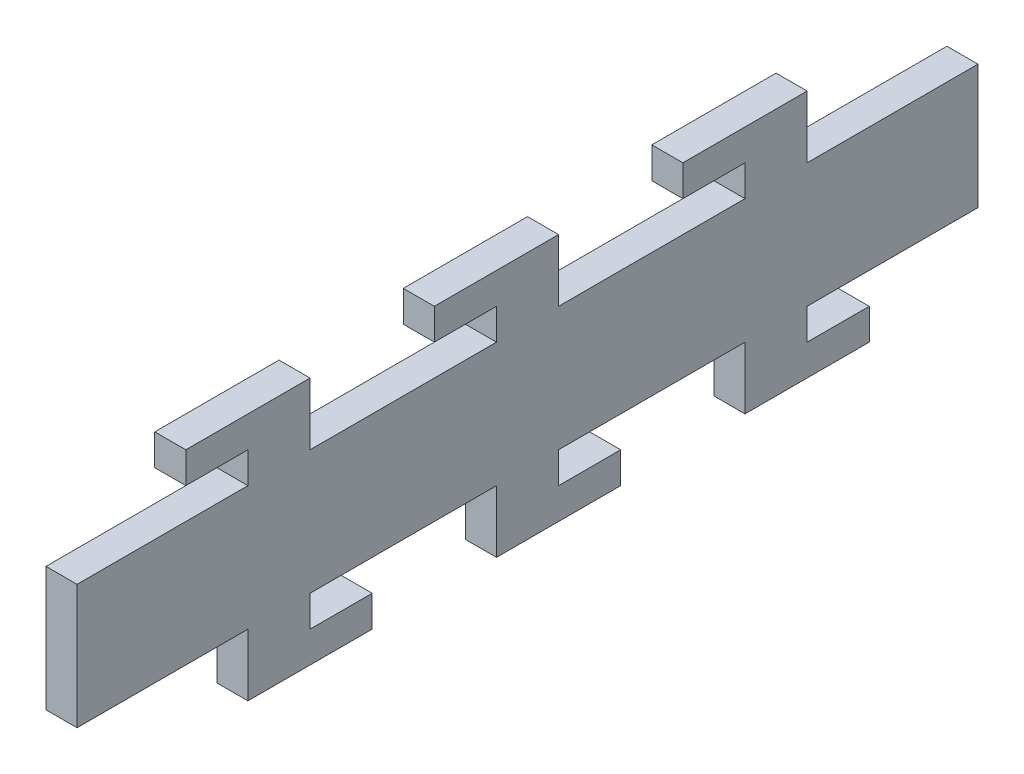
SolidWorks part; units mm, degrees
ref_plane "Plan de face" through (0, 0, 0) normal (0, 0, 1) x (1, 0, 0)
ref_plane "Plan de dessus" through (0, 0, 0) normal (0, 1, 0) x (1, 0, 0)
ref_plane "Plan de droite" through (0, 0, 0) normal (1, 0, 0) x (0, 0, -1)
sketch "Esquisse1" plane through (0, 0, 0) normal (1, 0, 0) x (0, 0, -1)
  line L0 (72.5, -10) -> (45, -10)
  line L1 (-72.5, 10) -> (72.5, 10) construction
  line L2 (-72.5, 10) -> (-72.5, -10)
  line L3 (-72.5, -10) -> (72.5, -10) construction
  line L4 (72.5, 10) -> (72.5, -10)
  line L5 (45, -10) -> (45, -15)
  line L6 (45, -15) -> (55, -15)
  line L7 (55, -15) -> (55, -20)
  line L8 (55, -20) -> (35, -20)
  line L9 (35, -20) -> (35, -10)
  line L10 (35, -10) -> (5, -10)
  line L11 (5, -10) -> (5, -15)
  line L12 (5, -15) -> (15, -15)
  line L13 (15, -15) -> (15, -20)
  line L14 (15, -20) -> (-5, -20)
  line L15 (-5, -20) -> (-5, -10)
  line L16 (-5, -10) -> (-35, -10)
  line L17 (-35, -10) -> (-35, -15)
  line L18 (-35, -15) -> (-25, -15)
  line L19 (-25, -15) -> (-25, -20)
  line L20 (-25, -20) -> (-45, -20)
  line L21 (-45, -20) -> (-45, -10)
  line L22 (-72.5, -10) -> (-45, -10)
  line L23 (-72.5, 10) -> (-45, 10)
  line L24 (-45, 10) -> (-45, 15)
  line L25 (-45, 15) -> (-55, 15)
  line L26 (-55, 15) -> (-55, 20)
  line L27 (-55, 20) -> (-35, 20)
  line L28 (-35, 20) -> (-35, 10)
  line L29 (-35, 10) -> (-5, 10)
  line L30 (-5, 10) -> (-5, 15)
  line L31 (-5, 15) -> (-15, 15)
  line L32 (-15, 15) -> (-15, 20)
  line L33 (-15, 20) -> (5, 20)
  line L34 (5, 20) -> (5, 10)
  line L35 (5, 10) -> (35, 10)
  line L36 (35, 10) -> (35, 15)
  line L37 (35, 15) -> (25, 15)
  line L38 (25, 15) -> (25, 20)
  line L39 (25, 20) -> (45, 20)
  line L40 (45, 20) -> (45, 10)
  line L41 (45, 10) -> (72.5, 10)
  dimension "D1" = 145
  dimension "D2" = 72.5
  dimension "D3" = 20
  dimension "D4" = 10
  dimension "D5" = 27.5
  dimension "D6" = 10
  dimension "D7" = 5
  dimension "D8" = 5
  dimension "D9" = 20
  dimension "D10" = 30
  dimension "D11" = 10
  dimension "D12" = 5
  dimension "D13" = 5
  dimension "D14" = 20
  dimension "D15" = 30
  dimension "D16" = 10
  dimension "D17" = 5
  dimension "D18" = 5
  dimension "D19" = 20
  dimension "D20" = 27.5
  dimension "D21" = 5
  dimension "D22" = 10
  dimension "D23" = 5
  dimension "D24" = 20
  dimension "D25" = 30
  dimension "D26" = 5
  dimension "D27" = 10
  dimension "D28" = 5
  dimension "D29" = 20
  dimension "D30" = 5
  dimension "D31" = 10
  dimension "D32" = 5
  dimension "D33" = 20
  dimension "D34" = 30
extrude "Boss.-Extru.1" add sketch "Esquisse1" along normal blind 5
